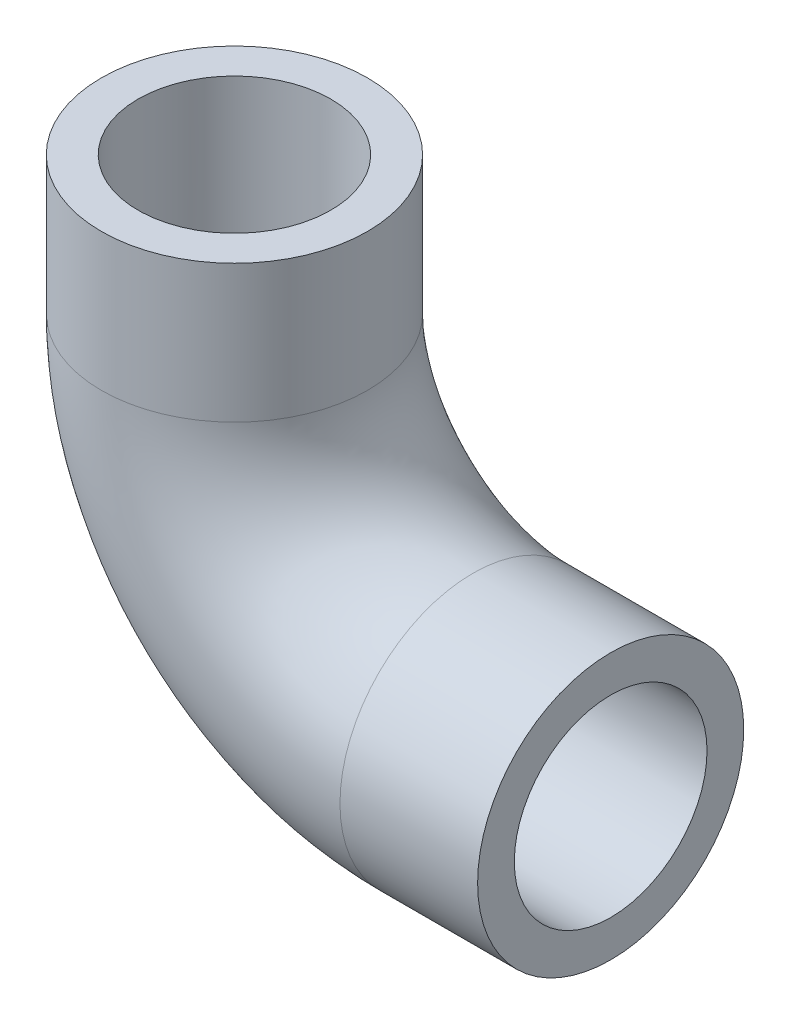
SolidWorks part; units mm, degrees
ref_plane "Front Plane" through (0, 0, 0) normal (0, 0, 1) x (1, 0, 0)
ref_plane "Top Plane" through (0, 0, 0) normal (0, 1, 0) x (1, 0, 0)
ref_plane "Right Plane" through (0, 0, 0) normal (1, 0, 0) x (0, 0, -1)
sketch "Sketch1" plane through (0, 0, 0) normal (0, 0, 1) x (1, 0, 0)
  line L0 (0, 0) -> (-150, 0)
  line L1 (-410, 260) -> (-410, 410)
  arc A0 (-150, 0) -> (-410, 260) centre (-150, 260) cw
  dimension "D3" = 260
  dimension "D1" = 150
  dimension "D2" = 150
sketch "Sketch2" plane through (0, 0, 0) normal (1, 0, 0) x (0, 0, -1)
  circle A0 centre (0, 0) radius 145
  dimension "D1" = 290
sweep "Sweep-Thin1" add path "Sketch1" circular profile diameter 290 parameters "D1"=40, "D3"=290
sketch "Sketch22" plane through (0, 0, 0) normal (1, 0, 0) x (0, 0, -1)
  line L1 (-180, 180) -> (180, 180)
  line L2 (-180, 180) -> (-180, -180)
  line L3 (-180, -180) -> (180, -180)
  line L4 (180, 180) -> (180, -180)
  line L5 (-180, 180) -> (180, -180) construction
  line L6 (-180, -180) -> (180, 180) construction
  point P0 (0, 0)
  dimension "D1" = 360
  dimension "D2" = 360
